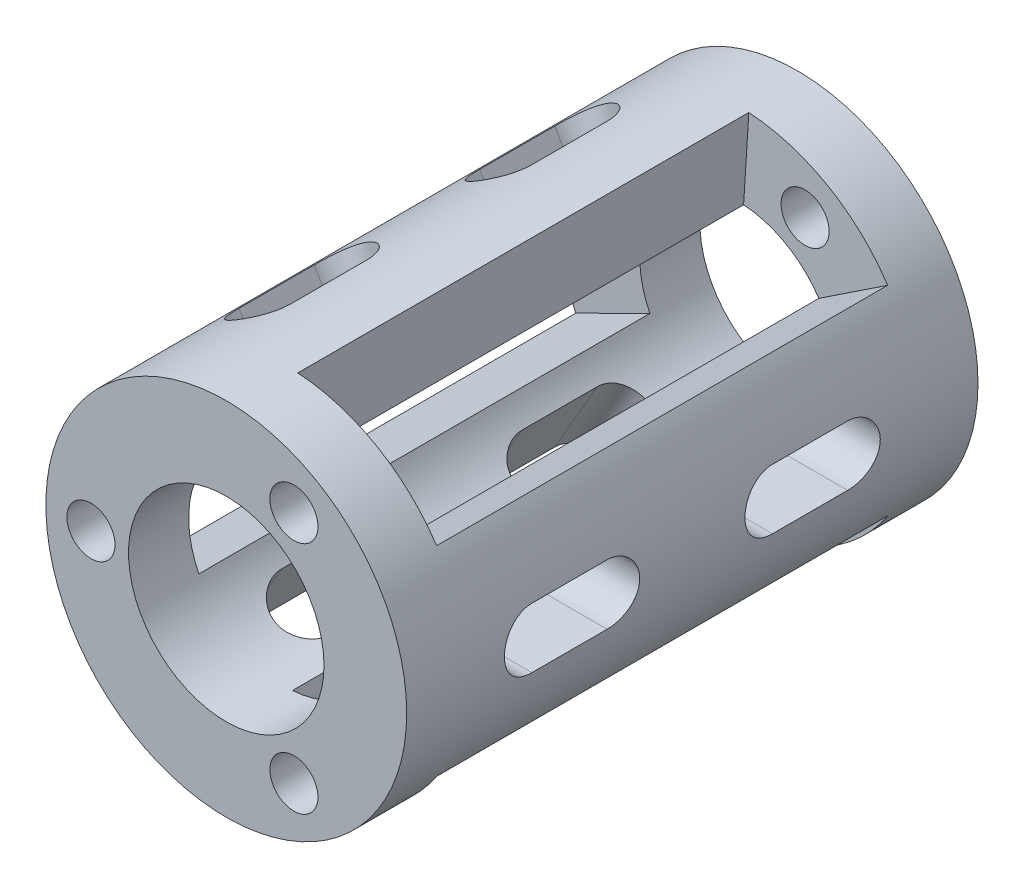
SolidWorks part; units mm, degrees
ref_plane "Alzado" through (0, 0, 0) normal (1, 0, 0) x (0, 1, 0)
ref_plane "Planta" through (0, 0, 0) normal (0, 0, 1) x (0, 1, 0)
ref_plane "Vista lateral" through (0, 0, 0) normal (0, 1, 0) x (-1, 0, 0)
sketch "Croquis1" plane through (0, 0, 0) normal (0, 0, 1) x (0, 1, 0)
  line L0 (0, 0) -> (0, 12) construction
  circle A0 centre (0, 0) radius 12
  circle A1 centre (0, 0) radius 6.5
  circle A2 centre (0, 0) radius 9 construction
  circle A5 centre (0, 9) radius 1.6
  circle A6 centre (7.7942, -4.5) radius 1.6
  circle A7 centre (-7.7942, -4.5) radius 1.6
  point P14 (0, 0)
  dimension "D1" = 24
  dimension "D2" = 13
  dimension "D3" = 18
  dimension "D4" = 3.2
  dimension "D5" = 3
extrude "Saliente-Extruir1" add sketch "Croquis1" along normal blind 4
sketch "Croquis2" plane through (0, 0, 4) normal (0, 0, 1) x (1, 0, 0)
  line L0 (0, 0) -> (-10.7497, -5.3333) construction
  line L1 (0, 0) -> (0.756, -11.9762) construction
  line L2 (-10.7497, -5.3333) -> (-5.8227, -2.8889)
  line L3 (0.756, -11.9762) -> (0.4095, -6.4871)
  line L4 (0.756, 11.9762) -> (0.4095, 6.4871)
  line L5 (-10.7497, 5.3333) -> (-5.8227, 2.8889)
  line L6 (9.9936, -6.6428) -> (5.4132, -3.5982)
  line L7 (9.9936, 6.6428) -> (5.4132, 3.5982)
  circle A3 centre (0, 0) radius 12
  circle A4 centre (0, 0) radius 6.5
  circle A5 centre (4.5, -7.7942) radius 1.6 construction
  circle A6 centre (-9, 0) radius 1.6 construction
  point P6 (0, 0)
  point P25 (0, 0)
  circle M2 centre (0, 0) radius 12
  circle M3 centre (0, 0) radius 6.5
  dimension "D2" = 4
  dimension "D3" = 13
  dimension "D4" = 24
  dimension "D1" = 4
  dimension "D5" = 3
extrude "Saliente-Extruir2" add sketch "Croquis2" along normal blind 30 contours L3 L2 M2 M3 | L5 L4 M2 M3 | L7 L6 M2 M3 region at (-4.4928, -7.7818, 4) region at (-4.4928, 7.7818, 4) region at (8.9856, 0, 4)
sketch "Croquis3" plane through (0, 0, 34) normal (0, 0, 1) x (1, 0, 0)
  circle A0 centre (0, 0) radius 6.5
  circle A2 centre (0, 0) radius 12
  circle A6 centre (-9, 0) radius 1.6
  circle A7 centre (4.5, 7.7942) radius 1.6
  circle A8 centre (4.5, -7.7942) radius 1.6
  dimension "D1" = 13
  dimension "D3" = 24
extrude "Saliente-Extruir3" add sketch "Croquis3" along normal blind 4
sketch "Croquis8" plane through (0, 0, 38) normal (0, 0, 1) x (1, 0, 0)
  line L0 (-18, 0) -> (0, 0) construction
  line L1 (-19.2732, 3.1526) -> (-9.7468, 7)
  line L2 (-19.2732, -3.1526) -> (-9.7468, -7)
  circle A0 centre (-18, 0) radius 1.6
  circle A1 centre (-18, 0) radius 3.4
  circle A2 centre (0, 0) radius 12 construction
  dimension "D1" = 3.2
  dimension "D2" = 1.8
  dimension "D3" = 7
  dimension "D4" = 18
sketch "Croquis7" plane through (0, 0, 0) normal (1, 0, 0) x (0, 1, 0)
  line L0 (0, 24.5) -> (0, 29.5) construction
  line L1 (-2, 24.5) -> (-2, 29.5)
  line L2 (2, 24.5) -> (2, 29.5)
  line L3 (-1.6573, 19) -> (10.6066, 19) construction
  line L4 (0, 13.5) -> (0, 8.5) construction
  line L5 (-2, 13.5) -> (-2, 8.5)
  line L7 (2, 13.5) -> (2, 8.5)
  line L8 (0, 0) -> (0, 38) construction
  line L9 (6.5, 38) -> (-6.5, 38) construction
  arc A0 (-2, 24.5) -> (2, 24.5) centre (0, 24.5) ccw
  arc A1 (2, 29.5) -> (-2, 29.5) centre (0, 29.5) ccw
  arc A2 (-2, 13.5) -> (2, 13.5) centre (0, 13.5) cw
  arc A3 (2, 8.5) -> (-2, 8.5) centre (0, 8.5) cw
  point P3 (0, 27)
  point P11 (0, 19)
  point P14 (0, 11)
  dimension "D1" = 8
  dimension "D2" = 5
  dimension "D3" = 4
extrude "Cortar-Extruir2" cut sketch "Croquis7" against normal mid plane 100
pattern_circular "MatrizC1" count 3 over 360 about axis through (0, 0, 4) along (0, 0, -1) of "Cortar-Extruir2"
